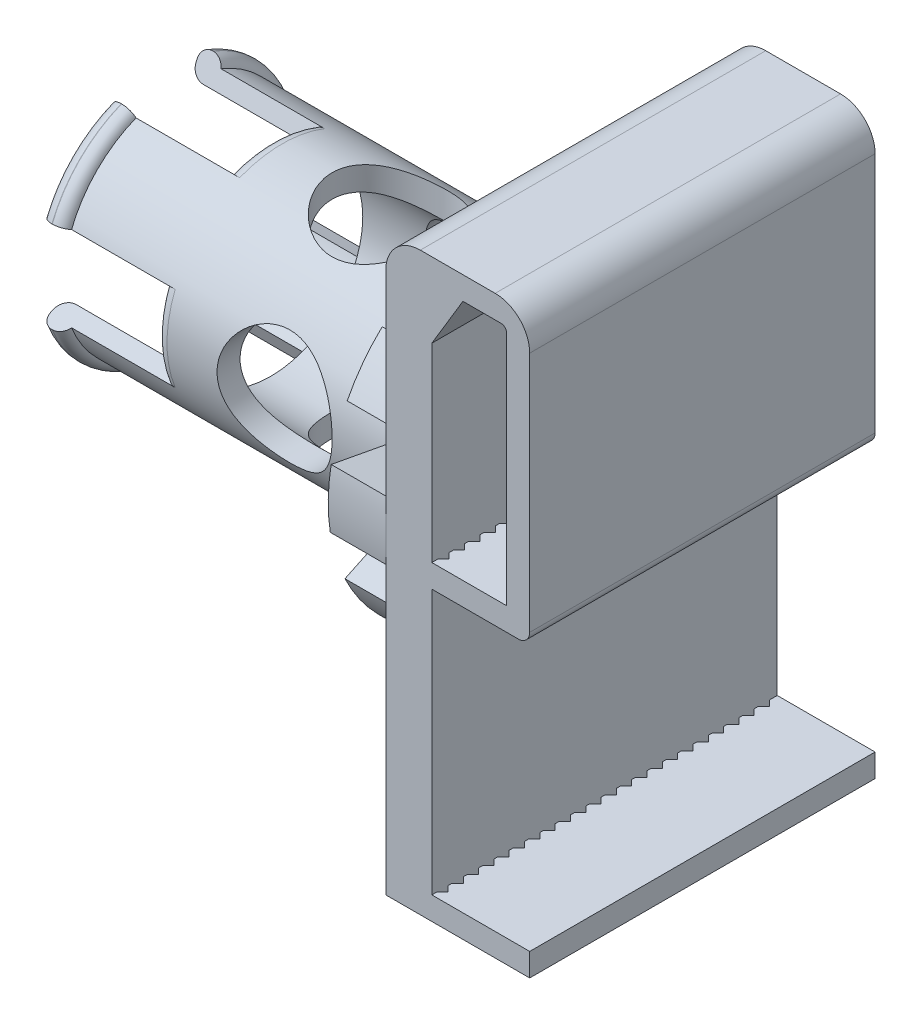
SolidWorks part; units mm, degrees
ref_plane "Front Plane" through (0, 0, 0) normal (0, 0, 1) x (1, 0, 0)
ref_plane "Top Plane" through (0, 0, 0) normal (0, 1, 0) x (1, 0, 0)
ref_plane "Right Plane" through (0, 0, 0) normal (1, 0, 0) x (0, 0, -1)
sketch "Sketch1" plane through (0, 0, 0) normal (0, 0, 1) x (1, 0, 0)
  line L0 (0, 0) -> (0, 50)
  line L1 (0, 50) -> (12.5, 50)
  line L2 (12.5, 50) -> (12.5, 25)
  line L3 (12.5, 25) -> (10.5, 25)
  line L4 (10.5, 25) -> (10.5, 48)
  line L5 (10.5, 48) -> (6.7, 48)
  line L6 (6.7, 48) -> (4, 43.5)
  line L7 (4, 43.5) -> (4, 0)
  line L8 (4, 0) -> (0, 0)
  dimension "D1" = 3.8
  dimension "D2" = 2.7
  dimension "D3" = 2
  dimension "D4" = 2
  dimension "D5" = 4
  dimension "D6" = 4.5
  dimension "D7" = 25
  dimension "D8" = 50
extrude "Boss-Extrude1" add sketch "Sketch1" along normal blind 30
fillet "Fillet1" radius 3 2 edges at (12.5, 50, 15) (0, 50, 15)
fillet "Fillet2" radius 0.5 1 edges at (10.5, 48, 15)
fillet "Fillet3" radius 1 1 edges at (12.5, 25, 15)
sketch "Sketch3" plane through (0, 0, 0) normal (-1, 0, 0) x (0, 0, 1)
  line L0 (30, 47) -> (0, 47) construction
  circle A0 centre (15, 27) radius 15
  dimension "D1" = 30
  dimension "D2" = 20
extrude "Boss-Extrude3" add sketch "Sketch3" along normal blind 5
sketch "Sketch4" plane through (-5, 0, 0) normal (-1, 0, 0) x (0, 0, 1)
  circle A0 centre (15, 27) radius 10
  dimension "D1" = 20
extrude "Boss-Extrude4" add sketch "Sketch4" along normal blind 30
sketch "Sketch6" plane through (-35, 0, 0) normal (-1, 0, 0) x (0, 0, 1)
  circle A0 centre (15, 27) radius 10.7604
extrude "Boss-Extrude5" add sketch "Sketch6" against normal blind 2
sketch "Sketch5" plane through (-35, 0, 0) normal (-1, 0, 0) x (0, 0, 1)
  circle A0 centre (15, 27) radius 8.5
  circle A1 centre (15, 27) radius 10 construction
  dimension "D1" = 17
  dimension "D2" = 1.5
extrude "Cut-Extrude1" cut sketch "Sketch5" against normal blind 10
fillet "Fillet4" radius 1 2 edges at (-33, 27, 25.7604) (-35, 27, 25.7604)
fillet "Fillet5" radius 1 1 edges at (-35, 27, 23.5)
sketch "Sketch8" plane through (-35, 0, 0) normal (-1, 0, 0) x (0, 0, 1)
  line L0 (12.0452, 34.4343) -> (11.0256, 36.9995)
  line L2 (18.9744, 36.9995) -> (17.9548, 34.4343)
  circle A0 centre (15, 27) radius 10.7604 construction
  arc A1 (18.9744, 36.9995) -> (11.0256, 36.9995) centre (15, 27) ccw
  arc A2 (17.9548, 34.4343) -> (12.0452, 34.4343) centre (15, 27) ccw
extrude "Cut-Extrude2" cut sketch "Sketch8" against normal blind 10
ref_axis "Axis1" through (-33, 27, 15) along (1, 0, 0)
pattern_circular "CirPattern3" count 4 over 360 about axis through (-33, 27, 15) along (1, 0, 0) of "Cut-Extrude2"
fillet "Fillet6" radius 1 4 edges at (-25, 27, 25) (-25, 17, 15) (-25, 27, 5) (-25, 37, 15)
sketch "Sketch9" plane through (-25, 0, 0) normal (-1, 0, 0) x (0, 0, 1)
  circle A0 centre (15, 27) radius 8
extrude "Cut-Extrude3" cut sketch "Sketch9" against normal up to surface (29 mm away) up to face at (4, 21.75, 15)
sketch "Sketch14" plane through (10.5, 0, 0) normal (-1, 0, 0) x (0, 0, 1)
  line L1 (0, 25) -> (7.254, 25)
  line L2 (0, 25) -> (0, 27)
  line L3 (0, 27) -> (7, 27)
  arc A0 (7, 27) -> (7.254, 25) centre (15, 27) ccw
  dimension "D1" = 2
extrude "Boss-Extrude7" add sketch "Sketch14" along normal up to next
sketch "Sketch16" plane through (0, 25, 0) normal (0, -1, 0) x (1, 0, 0)
  line L0 (4, 0.5) -> (4.5, 1)
  line L1 (4, 0) -> (4, 7.254) construction
  line L2 (4.5, 1) -> (4, 1.5)
  line L3 (4, 1.5) -> (4, 0.5)
  dimension "D1" = 0.5
  dimension "D2" = 1
  dimension "D3" = 45
  dimension "D4" = 0.5
extrude "Cut-Extrude7" cut sketch "Sketch16" against normal up to next
pattern_linear "LPattern3" count 5 spacing 1.35 along (0, 0, 1) of "Cut-Extrude7"
sketch "Sketch17" plane through (0, 25, 0) normal (0, -1, 0) x (1, 0, 0)
  line L0 (10.5, 0.5) -> (10, 1)
  line L1 (10, 1) -> (10.5, 1.5)
  line L2 (10.5, 1.5) -> (10.5, 0.5)
  line L4 (10.5, 30) -> (10.5, 0) construction
  line L5 (4, 0) -> (11.5, 0) construction
  dimension "D1" = 0.5
  dimension "D2" = 1
extrude "Cut-Extrude8" cut sketch "Sketch17" against normal up to next
pattern_linear "LPattern4" count 5 spacing 1.35 along (0, 0, 1) of "Cut-Extrude8"
sketch "Sketch19" plane through (10.5, 0, 0) normal (-1, 0, 0) x (0, 0, 1)
  line L1 (30, 25) -> (22.746, 25)
  line L2 (30, 25) -> (30, 27)
  line L3 (30, 27) -> (23, 27)
  arc A0 (22.746, 25) -> (23, 27) centre (15, 27) ccw
extrude "Boss-Extrude8" add sketch "Sketch19" along normal up to surface (6.5 mm away) up to face at (4, 26, 5.725)
pattern_linear "LPattern5" count 2 spacing 22.6 along (0, 0, 1) of "LPattern4"
pattern_linear "LPattern6" count 2 spacing 22.6 along (0, 0, 1) of "LPattern3"
sketch "Sketch20" plane through (0, 0, 0) normal (0, -1, 0) x (1, 0, 0)
  line L1 (4, 30) -> (12.5, 30)
  line L2 (4, 30) -> (4, 0)
  line L3 (4, 0) -> (12.5, 0)
  line L4 (12.5, 30) -> (12.5, 0)
extrude "Boss-Extrude9" add sketch "Sketch20" against normal blind 2
sketch "Sketch21" plane through (0, 0, 0) normal (0, -1, 0) x (1, 0, 0)
  line L0 (4, 29.6) -> (4, 28.6)
  line L1 (4, 28.6) -> (4.5, 29.1)
  line L2 (4.5, 29.1) -> (4, 29.6)
  line L3 (12.5, 0) -> (12.5, 30) construction
  line L4 (0, 30) -> (12.5, 30) construction
  dimension "D1" = 8.5
  dimension "D2" = 0.4
  dimension "D3" = 1
  dimension "D4" = 0.5
  dimension "D5" = 315
extrude "Cut-Extrude9" cut sketch "Sketch21" against normal up to next
pattern_linear "LPattern7" count 22 spacing 1.33 along (0, 0, -1) of "Cut-Extrude9"
sketch "Sketch22" plane through (-5, 0, 0) normal (-1, 0, 0) x (0, 0, 1)
  line L0 (13.4167, 36.8739) -> (12.625, 41.8108)
  line L2 (16.9414, 41.8738) -> (16.2943, 36.9159)
  circle A0 centre (15, 27) radius 15 construction
  arc A1 (16.2943, 36.9159) -> (13.4167, 36.8739) centre (15, 27) ccw
  arc A2 (16.9414, 41.8738) -> (12.625, 41.8108) centre (15, 27) ccw
extrude "Cut-Extrude10" cut sketch "Sketch22" against normal up to surface (5 mm away) up to face at (0, 40.75, 15)
pattern_circular "CirPattern4" count 10 over 360 about axis through (-33, 27, 15) along (1, 0, 0) of "Cut-Extrude10"
sketch "Sketch23" plane through (0, 0, 0) normal (0, 0, 1) x (1, 0, 0)
  line L0 (-33, 27) -> (-5, 27) construction
  circle A0 centre (-14.6614, 27) radius 5
  dimension "D1" = 10
extrude "Cut-Extrude11" cut sketch "Sketch23" along normal through all
pattern_circular "CirPattern5" count 4 over 360 about axis through (-33, 27, 15) along (1, 0, 0) of "Cut-Extrude11"
